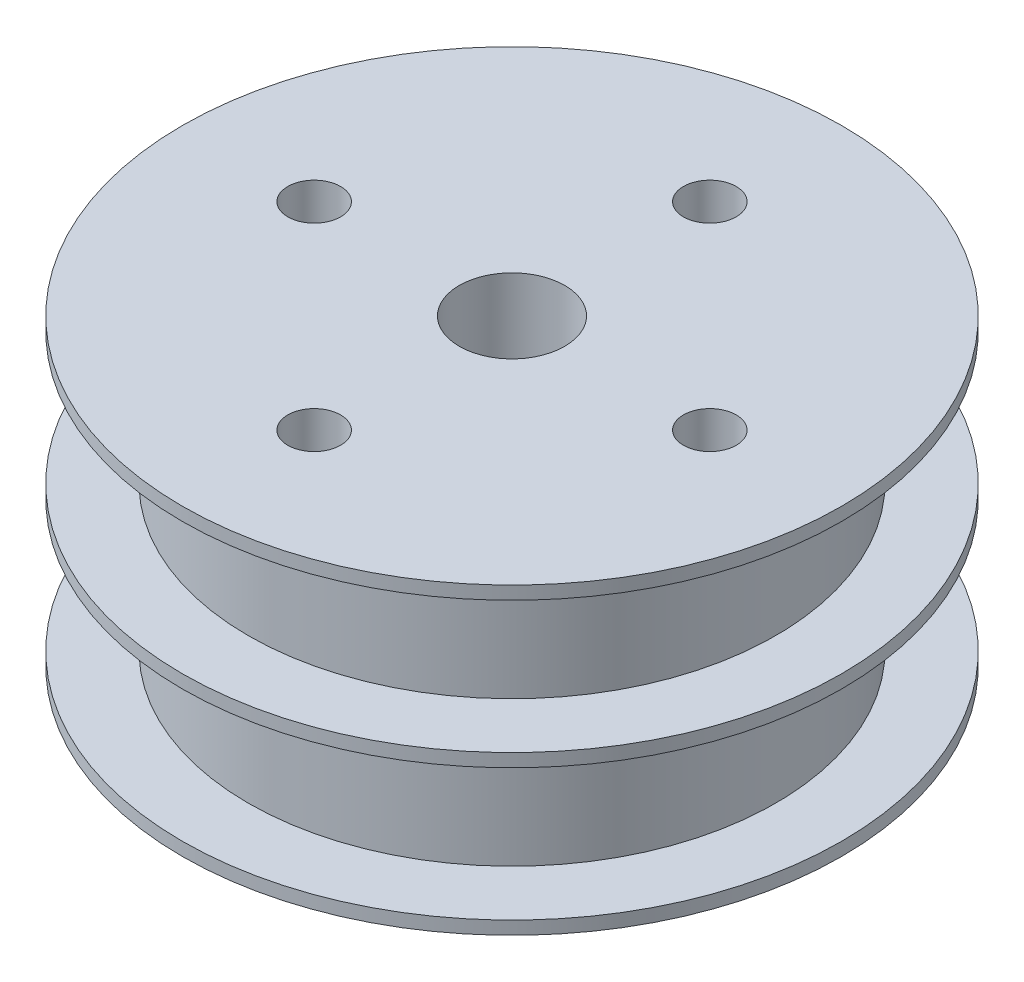
SolidWorks part; units mm, degrees
material "尼龙 6/10"
ref_plane "前视基准面" through (0, 0, 0) normal (0, 0, 1) x (1, 0, 0)
ref_plane "上视基准面" through (0, 0, 0) normal (0, 1, 0) x (1, 0, 0)
ref_plane "右视基准面" through (0, 0, 0) normal (1, 0, 0) x (0, 0, -1)
sketch "草图1" plane through (0, 0, 0) normal (0, 1, 0) x (1, 0, 0)
  circle A0 centre (0, 0) radius 20
  circle A1 centre (0, 15) radius 2
  circle A2 centre (15, 0) radius 2
  circle A3 centre (0, -15) radius 2
  circle A4 centre (-15, 0) radius 2
  circle A5 centre (0, 0) radius 4
  point P14 (0, 0)
  dimension "D1" = 40
  dimension "D2" = 4
  dimension "D3" = 15
  dimension "D5" = 8
  dimension "D4" = 4
extrude "凸台-拉伸1" add sketch "草图1" along normal blind 10
sketch "草图2" plane through (0, 10, 0) normal (0, 1, 0) x (1, 0, 0)
  circle A0 centre (0, 0) radius 25
  circle A1 centre (0, 0) radius 4
  circle A2 centre (-15, 0) radius 2
  circle A3 centre (0, 15) radius 2
  circle A4 centre (15, 0) radius 2
  circle A5 centre (0, -15) radius 2
  point P16 (0, 0)
  dimension "D1" = 50
  dimension "D2" = 4
  dimension "D3" = 8
  dimension "D5" = 15
  dimension "D4" = 4
extrude "凸台-拉伸2" add sketch "草图2" along normal blind 1
sketch "草图3" plane through (0, 0, 0) normal (0, -1, 0) x (1, 0, 0)
  circle A0 centre (0, 0) radius 25
  circle A1 centre (0, 0) radius 4
  circle A2 centre (15, 0) radius 2
  circle A3 centre (0, -15) radius 2
  circle A4 centre (-15, 0) radius 2
  circle A5 centre (0, 15) radius 2
  point P16 (0, 0)
  dimension "D1" = 50
  dimension "D2" = 8
  dimension "D3" = 4
  dimension "D4" = 4
extrude "凸台-拉伸3" add sketch "草图3" along normal blind 1
sketch "草图4" plane through (0, -1, 0) normal (0, -1, 0) x (1, 0, 0)
  circle A0 centre (0, 0) radius 20
  circle A1 centre (0, 15) radius 2
  circle A2 centre (15, 0) radius 2
  circle A3 centre (0, -15) radius 2
  circle A4 centre (-15, 0) radius 2
  circle A5 centre (0, 0) radius 4
  point P15 (0, 0)
  dimension "D1" = 40
  dimension "D2" = 4
  dimension "D4" = 8
  dimension "D3" = 4
extrude "凸台-拉伸4" add sketch "草图4" along normal blind 10
sketch "草图5" plane through (0, -11, 0) normal (0, -1, 0) x (1, 0, 0)
  circle A0 centre (0, 0) radius 25
  circle A3 centre (15, 0) radius 2
  circle A4 centre (0, -15) radius 2
  circle A5 centre (-15, 0) radius 2
  circle A6 centre (0, 15) radius 2
  circle A7 centre (0, 0) radius 4
  point P16 (0, 0)
  dimension "D1" = 50
  dimension "D2" = 4
  dimension "D3" = 8
extrude "凸台-拉伸5" add sketch "草图5" along normal blind 1
